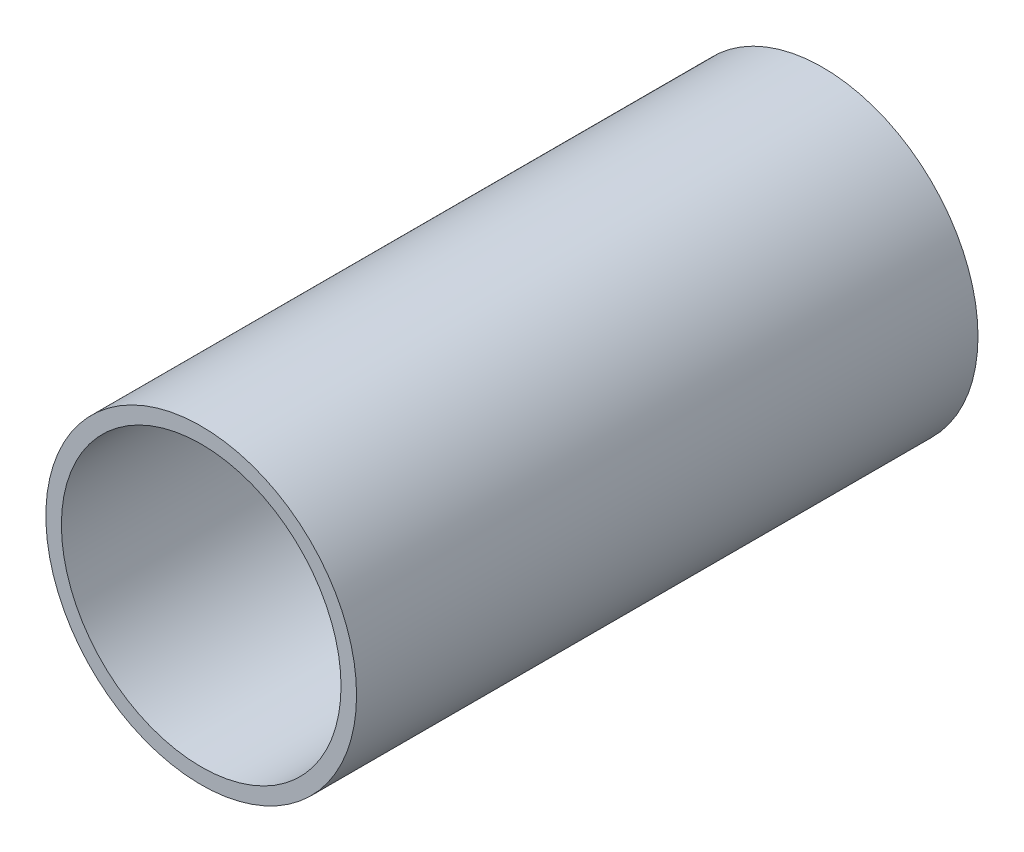
SolidWorks part; units mm, degrees
material "PVC Rigid"
ref_plane "Front Plane" through (0, 0, 0) normal (0, 0, 1) x (1, 0, 0)
ref_plane "Top Plane" through (0, 0, 0) normal (0, 1, 0) x (1, 0, 0)
ref_plane "Right Plane" through (0, 0, 0) normal (1, 0, 0) x (0, 0, -1)
sketch "Sketch1" plane through (0, 0, 0) normal (0, 0, 1) x (1, 0, 0)
  circle A0 centre (0, 0) radius 25.4
  circle A1 centre (0, 0) radius 22.86
  dimension "D1" = 50.8
  dimension "D2" = 2.54
extrude "Boss-Extrude1" add sketch "Sketch1" along normal mid plane 101.6
